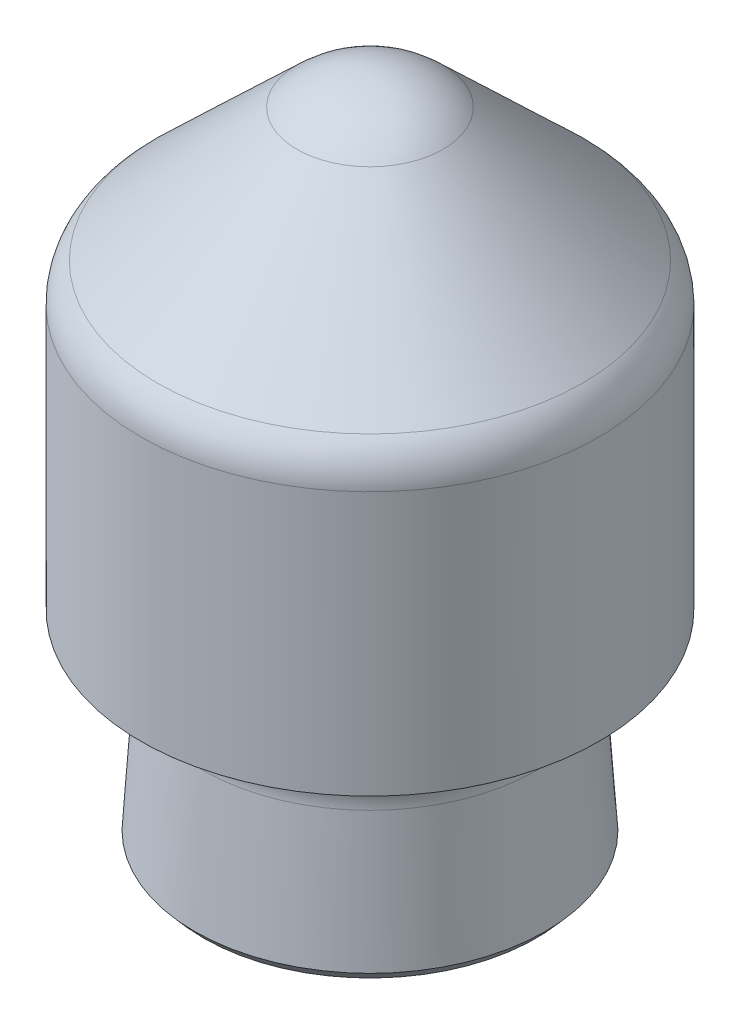
SolidWorks part; units mm, degrees
material "6061-T6 (SS)"
ref_plane "Front Plane" through (0, 0, 0) normal (0, 0, 1) x (1, 0, 0)
ref_plane "Top Plane" through (0, 0, 0) normal (0, 1, 0) x (1, 0, 0)
ref_plane "Right Plane" through (0, 0, 0) normal (1, 0, 0) x (0, 0, -1)
sketch "Sketch1" plane through (0, 0, 0) normal (0, 0, 1) x (1, 0, 0)
  line L0 (0, 25.4) -> (0, 41.3512) construction
  line L2 (4.7085, 14.7066) -> (-4.7085, 14.7066) construction
  line L3 (0, 25.4) -> (-4.2164, 25.4)
  line L4 (-3.899, 30.2387) -> (-4.2164, 25.4)
  line L5 (0, 25.4) -> (0, 41.3512)
  line L6 (-3.899, 30.2387) -> (-5.4864, 30.2387)
  line L7 (-5.4864, 30.2387) -> (-5.4864, 37.0967)
  line L8 (-1.7509, 40.6513) -> (-5.4864, 37.0967)
  arc A0 (-1.7509, 40.6513) -> (0, 41.3512) centre (0, 38.8112) cw
  point P2 (0, 0)
  point P8 (0, 0)
  dimension "D6" = 2.54
  dimension "D1" = 26.6446
  dimension "D2" = 3.899
  dimension "D3" = 10.9728
  dimension "D4" = 4.2545
  dimension "D5" = 11.1125
  dimension "D7" = 1.27
revolve "Revolve1" add sketch "Sketch1" angle 360 about L0
fillet "Fillet1" radius 1.27 1 edges at (0, 37.0967, -5.4864)
fillet "Fillet2" radius 1.27 1 edges at (0, 30.2387, -3.899)
chamfer "Chamfer1" distance 0.254 angle 45 1 edges at (0, 25.4, -4.2164) first distance on face at (0, 28.8856, -3.9878)
sketch "Sketch4" plane through (0, 25.4, 0) normal (0, -1, 0) x (1, 0, 0)
  circle A0 centre (0, 0) radius 3.5
  dimension "D1" = 7
extrude "Cut-Extrude1" cut sketch "Sketch4" against normal blind 2.5
hole_wizard "M7x0.75 Tapped Hole1" positions "Sketch5" profile "Sketch6" tap size "M7x1.0" standard "ANSI Metric"
sketch "Sketch5" plane through (0, 25.4, 0) normal (0, -1, 0) x (-1, 0, 0)
  point P0 (0, 0)
  point P3 (96.1394, -180.6847)
sketch "Sketch6" plane through (0, 25.4, 0) normal (1, 0, 0) x (0, 0, -1)
  line L0 (0, 0) -> (0, 12.7566)
  line L1 (0, 12.7566) -> (3, 10.954)
  line L2 (3, 10.954) -> (3, 0)
  line L5 (3, 0) -> (0, 0)
  line L10 (0, 12.7566) -> (-3, 10.954) construction
  line L11 (0, -6.35) -> (0, 107.95) construction
  dimension "Tap Drill Dia." = 6
  dimension "Tap Drill Depth" = 10.954
  dimension "Drill Angle" = 118
cosmetic thread "Hole Thread1" parameters "D1"=9.906, "D2"=7
